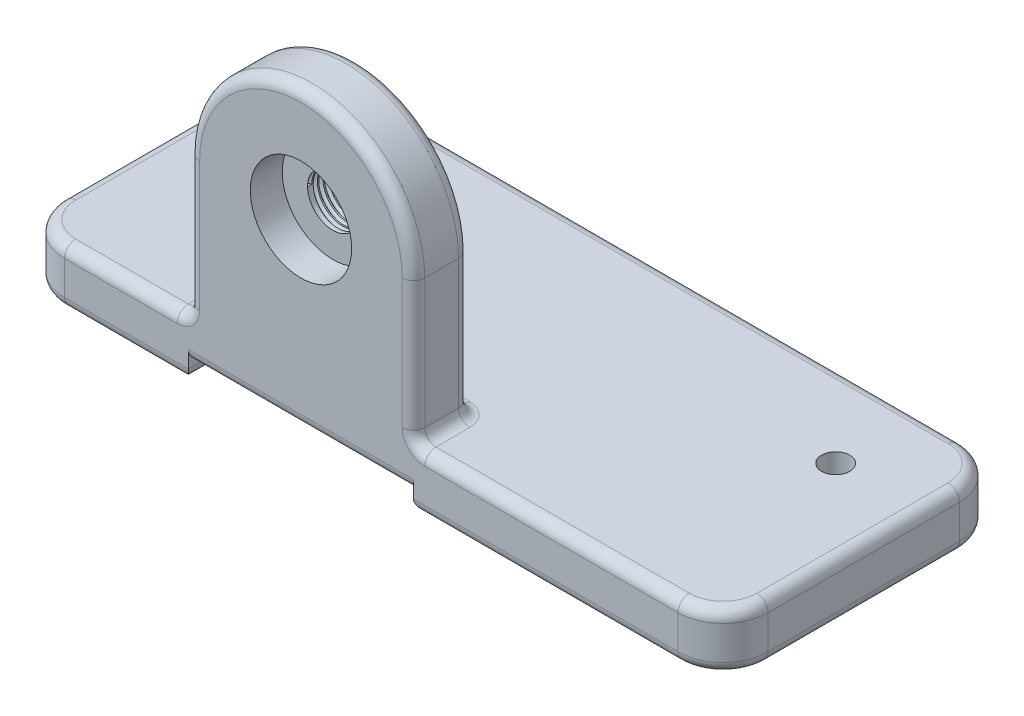
SolidWorks part; units mm, degrees
ref_plane "Front Plane" through (0, 0, 0) normal (0, 0, 1) x (1, 0, 0)
ref_plane "Top Plane" through (0, 0, 0) normal (0, 1, 0) x (1, 0, 0)
ref_plane "Right Plane" through (0, 0, 0) normal (1, 0, 0) x (0, 0, -1)
sketch "Sketch2" plane through (0, 0, 0) normal (0, 1, 0) x (1, 0, 0)
  line L1 (0, 0) -> (125, 0)
  line L2 (0, 0) -> (0, 50)
  line L3 (0, 50) -> (125, 50)
  line L4 (125, 0) -> (125, 50)
  dimension "D1" = 125
  dimension "D2" = 50
extrude "Boss-Extrude1" add sketch "Sketch2" along normal blind 10
sketch "Sketch4" plane through (0, 0, 0) normal (0, 0, 1) x (1, 0, 0)
  line L0 (30, 0) -> (30, 35)
  line L1 (0, 0) -> (125, 0) construction
  line L2 (70, 35) -> (70, 0)
  line L3 (30, 0) -> (70, 0)
  line L4 (0, 10) -> (0, 0) construction
  arc A0 (30, 35) -> (70, 35) centre (50, 35) cw
  dimension "D1" = 20
  dimension "D2" = 35
  dimension "D3" = 50
extrude "Boss-Extrude2" add sketch "Sketch4" against normal blind 10 contours L3 L2 A0 L0
sketch "Sketch5" plane through (0, 0, 0) normal (0, 0, 1) x (1, 0, 0)
  line L0 (0, 0) -> (125, 0) construction
  line L1 (30, 3) -> (70, 3)
  line L2 (30, 3) -> (30, 0)
  line L3 (30, 0) -> (70, 0)
  line L4 (70, 3) -> (70, 0)
  line L5 (30, 10) -> (30, 35) construction
  dimension "D1" = 40
  dimension "D2" = 3
extrude "Cut-Extrude1" cut sketch "Sketch5" against normal through all
hole_wizard "CBORE for M8 Hex Head Bolt1" positions "Sketch6" profile "Sketch7" counterbore size "M8" standard "ANSI Metric" end condition through all
sketch "Sketch6" plane through (0, 0, 0) normal (0, 0, 1) x (1, 0, 0)
  arc A0 (70, 35) -> (30, 35) centre (50, 35) ccw construction
  point P0 (50, 35)
sketch "Sketch7" plane through (50, 35, 0) normal (1, 0, 0) x (0, -1, 0)
  line L0 (0, 0) -> (0, 50)
  line L1 (0, 50) -> (4.5, 50)
  line L3 (4.5, 50) -> (4.5, 5.68)
  line L4 (4.5, 5.68) -> (9.005, 5.68)
  line L5 (9.005, 5.68) -> (9.005, 0)
  line L7 (9.005, 0) -> (0, 0)
  line L11 (0, -6.35) -> (0, 107.95) construction
  dimension "Thru Hole Dia." = 9
  dimension "Thru Hole Depth" = 50
  dimension "C'Bore Dia." = 18.01
  dimension "C'Bore Depth" = 5.68
thread "Thread1" pitch 1 method cut profile "Thread Profile2" start angle 0, offset 0, length 10, pitch 1, diameter 9
ref_plane "Plane2" through (45.5, 35, -5.68) normal (0, -1, 0) x (-1, 0, 0)
sketch "Thread Profile2" plane through (45.5, 35, -5.68) normal (0, -1, 0) x (-1, 0, 0)
  line L0 (0, 0) -> (0, 1) construction
  line L1 (0, 0) -> (0.5413, 0.3125)
  line L2 (0.5413, 0.3125) -> (0.5413, 0.4375)
  line L3 (0.5413, 0.4375) -> (0, 0.75)
  line L4 (0.5413, 0.375) -> (0, 0.375) construction
  line L11 (0, 0) -> (0, 0.75)
  point P2 (0, 0)
  dimension "Pitch" = 1
  dimension "Profile_Angle" = 60
  dimension "Profile_Land" = 0.125
  dimension "Profile_Height" = 0.5413
hole_wizard "Ø5.0mm Dowel Hole2" positions "Sketch10" profile "Sketch11" hole size "Ø5.0" standard "ANSI Metric"
sketch "Sketch10" plane through (0, 10, 0) normal (0, 1, 0) x (1, 0, 0)
  line L0 (125, 50) -> (0, 50) construction
  line L1 (0, 50) -> (0, 0) construction
  line L2 (125, 0) -> (125, 50) construction
  point P0 (15, 35)
  point P2 (110, 35)
  point P5 (0, 0)
  dimension "D1" = 15
  dimension "D2" = 15
  dimension "D3" = 15
sketch "Sketch11" plane through (15, 10, -35) normal (1, 0, 0) x (0, 0, 1)
  line L0 (0, 0) -> (0, 6.5022)
  line L1 (0, 6.5022) -> (2.5, 5)
  line L2 (2.5, 5) -> (2.5, 0)
  line L5 (2.5, 0) -> (0, 0)
  line L10 (0, 6.5022) -> (-2.5, 5) construction
  line L11 (0, -6.35) -> (0, 107.95) construction
  dimension "Hole Dia." = 5
  dimension "Hole Depth" = 5
  dimension "Drill Angle" = 118
fillet "Fillet2" radius 2 24 edges at (50, 55, 0) (30, 22.5, 0) (70, 22.5, 0) (15, 10, 0) (0, 10, -25) (62.5, 10, -50) (125, 10, -25) (97.5, 10, 0) (70, 10, -5) (50, 10, -10) (30, 10, -5) (30, 22.5, -10) (70, 22.5, -10) (50, 55, -10) (97.5, 0, 0) (125, 0, -25) (97.5, 0, -50) (70, 0, -25) (15, 0, -50) (0, 0, -25) (15, 0, 0) (30, 0, -25) (50, 3, -50) (50, 3, 0)
fillet "Fillet3" radius 8 12 edges at (124.4142, 9.4142, -49.4142) (124.4142, 9.4142, -0.5858) (0.5858, 9.4142, -49.4142) (0.5858, 9.4142, -0.5858) (0, 5, 0) (0, 5, -50) (125, 5, 0) (125, 5, -50) (124.4142, 0.5858, -49.4142) (124.4142, 0.5858, -0.5858) (0.5858, 0.5858, -49.4142) (0.5858, 0.5858, -0.5858)
